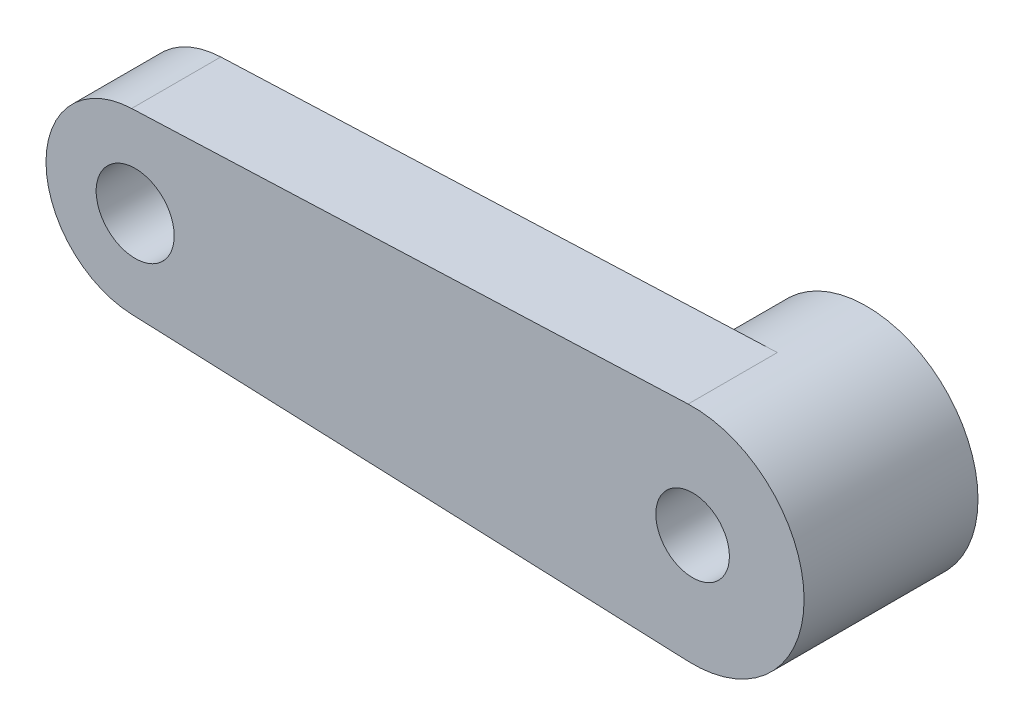
SolidWorks part; units mm, degrees
ref_plane "Front Plane" through (0, 0, 0) normal (0, 0, 1) x (1, 0, 0)
ref_plane "Top Plane" through (0, 0, 0) normal (0, 1, 0) x (1, 0, 0)
ref_plane "Right Plane" through (0, 0, 0) normal (1, 0, 0) x (0, 0, -1)
sketch "Sketch1" plane through (0, 0, 0) normal (0, 0, 1) x (1, 0, 0)
  line L96 (0.2308, 2.8251) -> (0.1696, 2.7453)
  line L97 (0.1696, 2.7453) -> (0.1212, 2.8292)
  line L98 (-0.1379, 2.8447) -> (-0.1902, 2.7542)
  line L99 (-0.1902, 2.7542) -> (-0.2514, 2.834)
  line L100 (-0.509, 2.8001) -> (-0.5474, 2.7072)
  line L101 (-0.5474, 2.7072) -> (-0.6186, 2.7783)
  line L102 (-0.8695, 2.7111) -> (-0.8955, 2.6139)
  line L103 (-0.8955, 2.6139) -> (-0.9753, 2.6752)
  line L104 (-1.2153, 2.5757) -> (-1.2285, 2.476)
  line L105 (-1.2285, 2.476) -> (-1.3156, 2.5263)
  line L106 (-1.5406, 2.3964) -> (-1.5406, 2.2958)
  line L107 (-1.5406, 2.2958) -> (-1.6335, 2.3343)
  line L108 (-1.8396, 2.1762) -> (-1.8265, 2.0765)
  line L109 (-1.8265, 2.0765) -> (-1.9236, 2.1025)
  line L110 (-2.1073, 1.9188) -> (-2.0813, 1.8216)
  line L111 (-2.0813, 1.8216) -> (-2.181, 1.8348)
  line L112 (-2.3391, 1.6287) -> (-2.3007, 1.5357)
  line L113 (-2.3007, 1.5357) -> (-2.4012, 1.5357)
  line L114 (-2.5311, 1.3107) -> (-2.4809, 1.2237)
  line L115 (-2.4809, 1.2237) -> (-2.5806, 1.2105)
  line L116 (-2.68, 0.9705) -> (-2.6188, 0.8907)
  line L117 (-2.6188, 0.8907) -> (-2.7159, 0.8647)
  line L118 (-2.7831, 0.6137) -> (-2.712, 0.5426)
  line L119 (-2.712, 0.5426) -> (-2.8049, 0.5041)
  line L120 (-2.8388, 0.2466) -> (-2.7591, 0.1853)
  line L121 (-2.7591, 0.1853) -> (-2.8462, 0.1351)
  line L122 (-2.8462, -0.1248) -> (-2.7591, -0.175)
  line L123 (-2.7591, -0.175) -> (-2.8388, -0.2363)
  line L124 (-2.8049, -0.4938) -> (-2.712, -0.5323)
  line L125 (-2.712, -0.5323) -> (-2.7831, -0.6034)
  line L126 (-2.7159, -0.8544) -> (-2.6188, -0.8804)
  line L127 (-2.6188, -0.8804) -> (-2.68, -0.9602)
  line L128 (-2.5806, -1.2002) -> (-2.4809, -1.2134)
  line L129 (-2.4809, -1.2134) -> (-2.5311, -1.3004)
  line L130 (-2.4012, -1.5254) -> (-2.3007, -1.5254)
  line L131 (-2.3007, -1.5254) -> (-2.3391, -1.6184)
  line L132 (-2.181, -1.8245) -> (-2.0813, -1.8113)
  line L133 (-2.0813, -1.8113) -> (-2.1073, -1.9085)
  line L134 (-1.9236, -2.0922) -> (-1.8265, -2.0662)
  line L135 (-1.8265, -2.0662) -> (-1.8396, -2.1659)
  line L136 (-1.6335, -2.324) -> (-1.5406, -2.2855)
  line L137 (-1.5406, -2.2855) -> (-1.5406, -2.3861)
  line L138 (-1.3156, -2.516) -> (-1.2285, -2.4657)
  line L139 (-1.2285, -2.4657) -> (-1.2153, -2.5654)
  line L140 (-0.9753, -2.6649) -> (-0.8955, -2.6036)
  line L141 (-0.8955, -2.6036) -> (-0.8695, -2.7008)
  line L142 (-0.6186, -2.768) -> (-0.5474, -2.6969)
  line L143 (-0.5474, -2.6969) -> (-0.509, -2.7898)
  line L144 (-0.2514, -2.8237) -> (-0.1902, -2.7439)
  line L145 (-0.1902, -2.7439) -> (-0.1399, -2.831)
  line L146 (0.1199, -2.831) -> (0.1702, -2.7439)
  line L147 (0.1702, -2.7439) -> (0.2314, -2.8237)
  line L148 (0.489, -2.7898) -> (0.5275, -2.6969)
  line L149 (0.5275, -2.6969) -> (0.5986, -2.768)
  line L150 (0.8496, -2.7008) -> (0.8756, -2.6036)
  line L151 (0.8756, -2.6036) -> (0.9554, -2.6649)
  line L152 (1.1954, -2.5654) -> (1.2085, -2.4657)
  line L153 (1.2085, -2.4657) -> (1.2956, -2.516)
  line L154 (1.5206, -2.3861) -> (1.5206, -2.2855)
  line L155 (1.5206, -2.2855) -> (1.6135, -2.324)
  line L156 (1.8197, -2.1659) -> (1.8065, -2.0662)
  line L157 (1.8065, -2.0662) -> (1.9037, -2.0922)
  line L158 (2.0874, -1.9085) -> (2.0613, -1.8113)
  line L159 (2.0613, -1.8113) -> (2.161, -1.8245)
  line L160 (2.3192, -1.6184) -> (2.2807, -1.5254)
  line L161 (2.2807, -1.5254) -> (2.3813, -1.5254)
  line L162 (2.5112, -1.3004) -> (2.4609, -1.2134)
  line L163 (2.4609, -1.2134) -> (2.5606, -1.2002)
  line L164 (2.66, -0.9602) -> (2.5988, -0.8804)
  line L165 (2.5988, -0.8804) -> (2.696, -0.8544)
  line L166 (2.7632, -0.6034) -> (2.6921, -0.5323)
  line L167 (2.6921, -0.5323) -> (2.785, -0.4938)
  line L168 (2.8189, -0.2363) -> (2.7391, -0.175)
  line L169 (2.7391, -0.175) -> (2.8315, -0.1217)
  line L170 (2.8304, 0.1234) -> (2.7385, 0.1764)
  line L171 (2.7385, 0.1764) -> (2.8183, 0.2376)
  line L172 (2.7844, 0.4952) -> (2.6915, 0.5337)
  line L173 (2.6915, 0.5337) -> (2.7626, 0.6048)
  line L174 (2.6953, 0.8557) -> (2.5982, 0.8818)
  line L175 (2.5982, 0.8818) -> (2.6594, 0.9615)
  line L176 (2.56, 1.2016) -> (2.4603, 1.2147)
  line L177 (2.4603, 1.2147) -> (2.5106, 1.3018)
  line L178 (2.3807, 1.5268) -> (2.2801, 1.5268)
  line L179 (2.2801, 1.5268) -> (2.3186, 1.6197)
  line L180 (2.1604, 1.8258) -> (2.0607, 1.8127)
  line L181 (2.0607, 1.8127) -> (2.0867, 1.9098)
  line L182 (1.903, 2.0935) -> (1.8059, 2.0675)
  line L183 (1.8059, 2.0675) -> (1.819, 2.1672)
  line L184 (1.6129, 2.3254) -> (1.52, 2.2869)
  line L185 (1.52, 2.2869) -> (1.52, 2.3875)
  line L186 (1.295, 2.5174) -> (1.2079, 2.4671)
  line L187 (1.2079, 2.4671) -> (1.1948, 2.5668)
  line L188 (0.9548, 2.6662) -> (0.875, 2.605)
  line L189 (0.875, 2.605) -> (0.8489, 2.7021)
  line L190 (0.598, 2.7694) -> (0.5269, 2.6983)
  line L191 (0.5269, 2.6983) -> (0.4884, 2.7912)
  arc A71 (0.1212, 2.8292) -> (-0.1379, 2.8447) centre (-0.0129, 2.7619) ccw
  arc A72 (-0.2514, 2.834) -> (-0.509, 2.8001) centre (-0.3704, 2.7427) ccw
  arc A73 (-0.6186, 2.7783) -> (-0.8695, 2.7111) centre (-0.7246, 2.6723) ccw
  arc A74 (-0.9753, 2.6752) -> (-1.2153, 2.5757) centre (-1.0666, 2.5562) ccw
  arc A75 (-1.3156, 2.5263) -> (-1.5406, 2.3964) centre (-1.3906, 2.3964) ccw
  arc A76 (-1.6335, 2.3343) -> (-1.8396, 2.1762) centre (-1.6909, 2.1957) ccw
  arc A77 (-1.9236, 2.1025) -> (-2.1073, 1.9188) centre (-1.9624, 1.9576) ccw
  arc A78 (-2.181, 1.8348) -> (-2.3391, 1.6287) centre (-2.2006, 1.6861) ccw
  arc A79 (-2.4012, 1.5357) -> (-2.5311, 1.3107) centre (-2.4012, 1.3857) ccw
  arc A80 (-2.5806, 1.2105) -> (-2.68, 0.9705) centre (-2.561, 1.0618) ccw
  arc A81 (-2.7159, 0.8647) -> (-2.7831, 0.6137) centre (-2.6771, 0.7198) ccw
  arc A82 (-2.8049, 0.5041) -> (-2.8388, 0.2466) centre (-2.7475, 0.3656) ccw
  arc A83 (-2.8462, 0.1351) -> (-2.8462, -0.1248) centre (-2.7712, 0.0051) ccw
  arc A84 (-2.8388, -0.2363) -> (-2.8049, -0.4938) centre (-2.7475, -0.3553) ccw
  arc A85 (-2.7831, -0.6034) -> (-2.7159, -0.8544) centre (-2.6771, -0.7095) ccw
  arc A86 (-2.68, -0.9602) -> (-2.5806, -1.2002) centre (-2.561, -1.0515) ccw
  arc A87 (-2.5311, -1.3004) -> (-2.4012, -1.5254) centre (-2.4012, -1.3754) ccw
  arc A88 (-2.3391, -1.6184) -> (-2.181, -1.8245) centre (-2.2006, -1.6758) ccw
  arc A89 (-2.1073, -1.9085) -> (-1.9236, -2.0922) centre (-1.9624, -1.9473) ccw
  arc A90 (-1.8396, -2.1659) -> (-1.6335, -2.324) centre (-1.6909, -2.1854) ccw
  arc A91 (-1.5406, -2.3861) -> (-1.3156, -2.516) centre (-1.3906, -2.3861) ccw
  arc A92 (-1.2153, -2.5654) -> (-0.9753, -2.6649) centre (-1.0666, -2.5459) ccw
  arc A93 (-0.8695, -2.7008) -> (-0.6186, -2.768) centre (-0.7246, -2.662) ccw
  arc A94 (-0.509, -2.7898) -> (-0.2514, -2.8237) centre (-0.3704, -2.7324) ccw
  arc A95 (-0.1399, -2.831) -> (0.1199, -2.831) centre (-0.01, -2.756) ccw
  arc A96 (0.2314, -2.8237) -> (0.489, -2.7898) centre (0.3504, -2.7324) ccw
  arc A97 (0.5986, -2.768) -> (0.8496, -2.7008) centre (0.7047, -2.662) ccw
  arc A98 (0.9554, -2.6649) -> (1.1954, -2.5654) centre (1.0467, -2.5459) ccw
  arc A99 (1.2956, -2.516) -> (1.5206, -2.3861) centre (1.3706, -2.3861) ccw
  arc A100 (1.6135, -2.324) -> (1.8197, -2.1659) centre (1.6709, -2.1854) ccw
  arc A101 (1.9037, -2.0922) -> (2.0874, -1.9085) centre (1.9425, -1.9473) ccw
  arc A102 (2.161, -1.8245) -> (2.3192, -1.6184) centre (2.1806, -1.6758) ccw
  arc A103 (2.3813, -1.5254) -> (2.5112, -1.3004) centre (2.3813, -1.3754) ccw
  arc A104 (2.5606, -1.2002) -> (2.66, -0.9602) centre (2.541, -1.0515) ccw
  arc A105 (2.696, -0.8544) -> (2.7632, -0.6034) centre (2.6571, -0.7095) ccw
  arc A106 (2.785, -0.4938) -> (2.8189, -0.2363) centre (2.7276, -0.3553) ccw
  arc A107 (2.8315, -0.1217) -> (2.8304, 0.1234) centre (2.7444, 0.0004) ccw
  arc A108 (2.8183, 0.2376) -> (2.7844, 0.4952) centre (2.727, 0.3566) ccw
  arc A109 (2.7626, 0.6048) -> (2.6953, 0.8557) centre (2.6565, 0.7108) ccw
  arc A110 (2.6594, 0.9615) -> (2.56, 1.2016) centre (2.5404, 1.0529) ccw
  arc A111 (2.5106, 1.3018) -> (2.3807, 1.5268) centre (2.3807, 1.3768) ccw
  arc A112 (2.3186, 1.6197) -> (2.1604, 1.8258) centre (2.18, 1.6771) ccw
  arc A113 (2.0867, 1.9098) -> (1.903, 2.0935) centre (1.9419, 1.9487) ccw
  arc A114 (1.819, 2.1672) -> (1.6129, 2.3254) centre (1.6703, 2.1868) ccw
  arc A115 (1.52, 2.3875) -> (1.295, 2.5174) centre (1.37, 2.3875) ccw
  arc A116 (1.1948, 2.5668) -> (0.9548, 2.6662) centre (1.0461, 2.5472) ccw
  arc A117 (0.8489, 2.7021) -> (0.598, 2.7694) centre (0.7041, 2.6633) ccw
  arc A118 (0.4884, 2.7912) -> (0.2308, 2.8251) centre (0.3498, 2.7338) ccw
  circle A119 centre (0, 0) radius 5
  dimension "D1" = 2.7453
  dimension "D2" = 10
extrude "Boss-Extrude1" add sketch "Sketch1" along normal blind 3.8
sketch "Sketch2" plane through (0, 0, 3.8) normal (0, 0, 1) x (1, 0, 0)
  line L0 (-25.16, 3.9968) -> (-0.2, 4.996)
  line L1 (-25.16, -3.9968) -> (-0.2, -4.996)
  circle A0 centre (0, 0) radius 1.65
  circle A2 centre (-25, 0) radius 1.75
  arc A3 (-25.16, 3.9968) -> (-25.16, -3.9968) centre (-25, 0) ccw
  circle A5 centre (0, 0) radius 5 construction
  arc A6 (-0.2, -4.996) -> (-0.2, 4.996) centre (0, 0) ccw
  dimension "D1" = 3.3
  dimension "D2" = 25
  dimension "D3" = 3.5
  dimension "D4" = 8
extrude "Boss-Extrude2" add sketch "Sketch2" along normal blind 4
